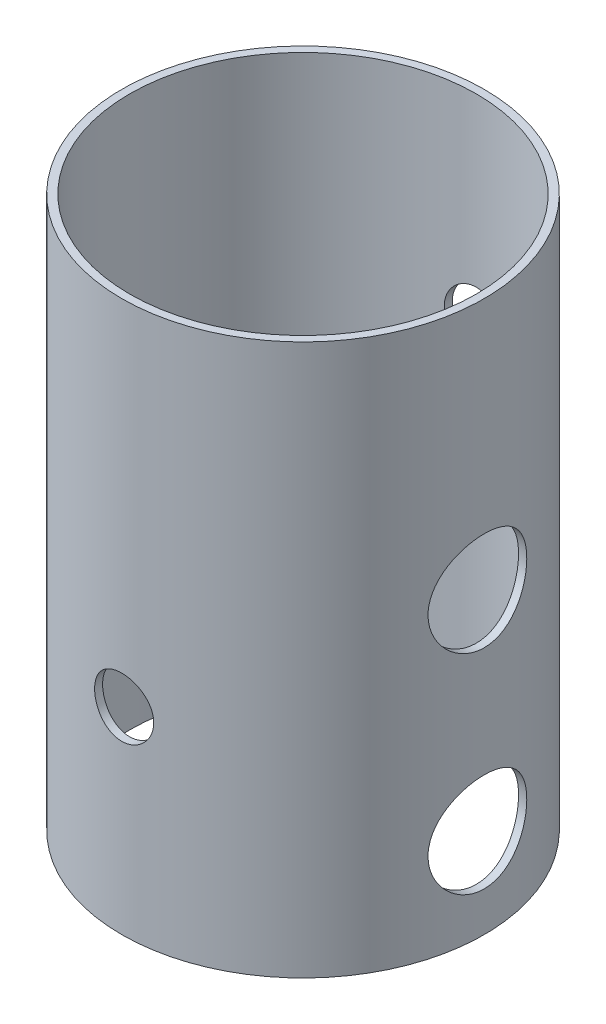
SolidWorks part; units mm, degrees
material "PTFE (general)"
ref_plane "Front Plane" through (0, 0, 0) normal (0, 0, 1) x (1, 0, 0)
ref_plane "Top Plane" through (0, 0, 0) normal (0, 1, 0) x (1, 0, 0)
ref_plane "Right Plane" through (0, 0, 0) normal (1, 0, 0) x (0, 0, -1)
sketch "Sketch1" plane through (0, 0, 0) normal (0, 1, 0) x (1, 0, 0)
  circle A0 centre (0, 0) radius 46
  circle A1 centre (0, 0) radius 44
  dimension "D1" = 92
  dimension "D2" = 88
extrude "Boss-Extrude1" add sketch "Sketch1" along normal blind 139.8
sketch "Sketch2" plane through (0, 0, 0) normal (1, 0, 0) x (0, 0, -1)
  line L1 (46, 139.8) -> (-46, 139.8) construction
  circle A0 centre (0, 22.6) radius 12.53
  circle A1 centre (0, 75.6) radius 12.53
  dimension "D2" = 25.06
  dimension "D3" = 25.06
  dimension "D1" = 64.2
  dimension "D5" = 53
extrude "Cut-Extrude1" cut sketch "Sketch2" along normal through all
sketch "Sketch4" plane through (0, 0, 0) normal (0, 0, 1) x (1, 0, 0)
  line L0 (-46, 0) -> (46, 0) construction
  circle A0 centre (0, 50) radius 7.5
  dimension "D1" = 15
  dimension "D2" = 50
extrude "Cut-Extrude2" cut sketch "Sketch4" along normal through all
sketch "Sketch5" plane through (0, 0, 0) normal (0, 0, 1) x (1, 0, 0)
  line L0 (46, 139.8) -> (-46, 139.8) construction
  circle A0 centre (0, 89.8) radius 7.5
  dimension "D1" = 15
  dimension "D2" = 50
extrude "Cut-Extrude3" cut sketch "Sketch5" against normal through all
